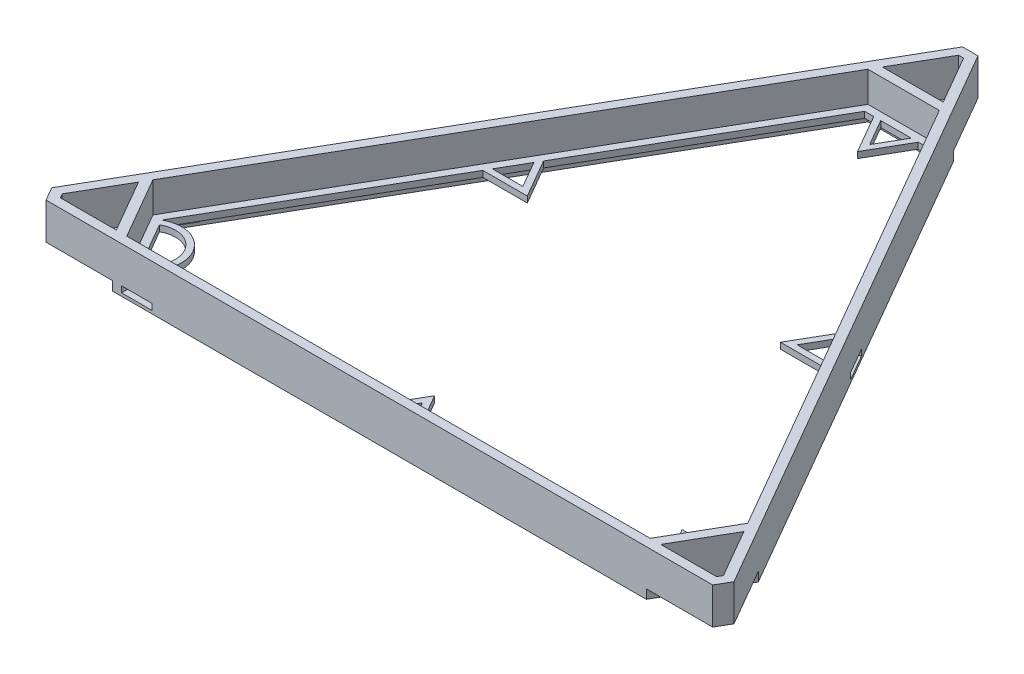
SolidWorks part; units mm, degrees
ref_plane "Front Plane" through (0, 0, 0) normal (0, 0, 1) x (1, 0, 0)
ref_plane "Top Plane" through (0, 0, 0) normal (0, 1, 0) x (1, 0, 0)
ref_plane "Right Plane" through (0, 0, 0) normal (1, 0, 0) x (0, 0, -1)
sketch "Sketch1" plane through (0, 0, 0) normal (0, 1, 0) x (1, 0, 0)
  line L17 (-4, 192.2576) -> (111, -6.9282) construction
  line L24 (4, 192.2576) -> (-111, -6.9282) construction
  line L25 (-115, 0) -> (115, 0) construction
  line L26 (0, -4.4282) -> (0, -1.4282) construction
  line L27 (-113, -3.4641) -> (-107, 0) construction
  line L28 (0, 192.2576) -> (0, 185.3294) construction
  line L29 (113, -3.4641) -> (107, 0) construction
  line L31 (-107.8246, -1.4282) -> (-108.6491, 0)
  line L39 (109.5566, -4.4282) -> (-109.5566, -4.4282)
  line L40 (-0.8246, 186.7576) -> (0.8246, 186.7576)
  line L41 (-109.5566, -4.4282) -> (-112.1132, 0)
  line L42 (-2.5566, 189.7576) -> (-112.1132, 0)
  line L43 (109.5566, -4.4282) -> (112.1132, 0)
  line L44 (-2.5566, 189.7576) -> (2.5566, 189.7576)
  line L45 (2.5566, 189.7576) -> (112.1132, 0)
  line L47 (108.6491, 0) -> (107.8246, -1.4282)
  line L50 (-99.4737, 15.8923) -> (-89.4737, -1.4282)
  line L51 (-107.8246, -1.4282) -> (-89.4737, -1.4282)
  line L52 (-99.4737, 15.8923) -> (-108.6491, 0)
  line L54 (89.4737, -1.4282) -> (107.8246, -1.4282)
  line L56 (89.4737, -1.4282) -> (99.4737, 15.8923)
  line L57 (99.4737, 15.8923) -> (108.6491, 0)
  line L58 (0, -1.4282) -> (0, 1.0718) construction
  line L59 (54.7369, 93.3788) -> (52.5718, 92.1288) construction
  line L62 (-10, 170.8653) -> (10, 170.8653)
  line L63 (-10, 170.8653) -> (-0.8246, 186.7576)
  line L64 (0.8246, 186.7576) -> (10, 170.8653)
  line L65 (94.4737, 7.2321) -> (91.8756, 8.7321) construction
  line L66 (-11.7321, 167.8653) -> (11.7321, 167.8653)
  line L67 (97.7417, 18.8923) -> (86.0096, -1.4282)
  line L68 (97.7417, 18.8923) -> (11.7321, 167.8653)
  line L69 (-54.7369, 93.3788) -> (-52.5718, 92.1288) construction
  line L71 (-94.4737, 7.2321) -> (-91.8756, 8.7321) construction
  line L72 (-97.7417, 18.8923) -> (-86.0096, -1.4282)
  line L73 (-86.0096, -1.4282) -> (86.0096, -1.4282)
  line L74 (-97.7417, 18.8923) -> (-11.7321, 167.8653)
  line L79 (91.8756, 8.7321) -> (89.7106, 9.9821) construction
  line L81 (0, 167.8653) -> (0, 165.3653) construction
  line L97 (-94.8549, 18.8923) -> (-84.5662, 1.0718) construction
  line L100 (-94.8549, 18.8923) -> (-93.8549, 17.1603) construction
  line L106 (-84.5662, 1.0718) -> (-85.5662, 2.8038) construction
  line L107 (-93.8549, 17.1603) -> (-85.5662, 2.8038)
  line L108 (50.0718, 96.4589) -> (55.0718, 87.7987)
  line L109 (41.6077, 85.7987) -> (56.2265, 85.7987)
  line L111 (50.0718, 96.4589) -> (45.0718, 87.7987)
  line L112 (45.0718, 87.7987) -> (55.0718, 87.7987)
  line L115 (56.2265, 85.7987) -> (94.8549, 18.8923)
  line L116 (48.9171, 98.4589) -> (10.2887, 165.3653)
  line L117 (41.6077, 85.7987) -> (48.9171, 98.4589)
  line L118 (-5, 165.3653) -> (5, 165.3653)
  line L121 (-55.0718, 87.7987) -> (-50.0718, 96.4589)
  line L122 (-5, 165.3653) -> (0, 156.7051)
  line L123 (5, 165.3653) -> (0, 156.7051)
  line L124 (-56.2265, 85.7987) -> (-94.8549, 18.8923)
  line L125 (0, 152.7051) -> (7.3094, 165.3653)
  line L126 (0, 152.7051) -> (-7.3094, 165.3653)
  line L127 (-10.2887, 165.3653) -> (-7.3094, 165.3653)
  line L128 (7.3094, 165.3653) -> (10.2887, 165.3653)
  line L129 (-50.0718, 96.4589) -> (-45.0718, 87.7987)
  line L130 (-55.0718, 87.7987) -> (-45.0718, 87.7987)
  line L131 (-48.9171, 98.4589) -> (-10.2887, 165.3653)
  line L132 (-41.6077, 85.7987) -> (-48.9171, 98.4589)
  line L133 (-41.6077, 85.7987) -> (-56.2265, 85.7987)
  line L134 (5, 1.0718) -> (-5, 1.0718)
  line L135 (-2.5, 5.4019) -> (-4.2321, 6.4019) construction
  line L136 (-5, 1.0718) -> (0, 9.7321)
  line L137 (0, 9.7321) -> (5, 1.0718)
  line L138 (2.5, 5.4019) -> (4.2321, 6.4019) construction
  line L139 (0, 13.7321) -> (-7.3094, 1.0718)
  line L141 (-7.3094, 1.0718) -> (-84.5662, 1.0718)
  line L143 (84.5662, 1.0718) -> (7.3094, 1.0718)
  line L144 (0, 13.7321) -> (7.3094, 1.0718)
  line L145 (92.2106, 14.3122) -> (87.2106, 5.6519)
  line L146 (84.7106, 9.9821) -> (82.9785, 8.9821) construction
  line L147 (87.2106, 5.6519) -> (82.2106, 14.3122)
  line L148 (82.2106, 14.3122) -> (92.2106, 14.3122)
  line L149 (87.2106, 14.3122) -> (87.2106, 16.3122) construction
  line L150 (94.8549, 18.8923) -> (93.3653, 16.3122)
  line L151 (78.7465, 16.3122) -> (86.0559, 3.6519)
  line L152 (78.7465, 16.3122) -> (93.3653, 16.3122)
  line L153 (86.0559, 3.6519) -> (84.5662, 1.0718)
  arc A0 (-94.8549, 18.8923) -> (-84.5662, 1.0718) centre (-89.7106, 9.9821) cw
  arc A1 (-93.8549, 17.1603) -> (-85.5662, 2.8038) centre (-89.7106, 9.9821) cw
  point P18 (0, -1.4282)
  point P41 (0, 167.8653)
  point P44 (91.8756, 8.7321)
  point P51 (-91.8756, 8.7321)
  point P55 (0, 1.0718)
  point P57 (-52.5718, 92.1288)
  point P61 (52.5718, 92.1288)
  point P65 (52.5718, 92.1288)
  point P69 (89.7106, 9.9821)
  point P74 (0, 165.3653)
  point P78 (-89.7106, 9.9821)
  point P79 (0, 165.3653)
  point P83 (-89.7106, 9.9821)
  point P89 (-52.5718, 92.1288)
  point P92 (0, 1.0718)
  point P97 (-45.8397, 93.1288)
  point P100 (-50.0718, 85.7987)
  point P106 (-4.2321, 6.4019)
  point P109 (4.2321, 6.4019)
  point P110 (89.7106, 9.9821)
  point P119 (82.9785, 8.9821)
  point P122 (87.2106, 16.3122)
  dimension "D1" = 8
  dimension "D2" = 8
  dimension "D3" = 8
  dimension "D4" = 230
  dimension "D5" = 230
  dimension "D6" = 230
  dimension "D7" = 3
  dimension "D8" = 3
  dimension "D9" = 3
  dimension "D10" = 2.5
  dimension "D11" = 2.5
  dimension "D12" = 2.5
  dimension "D13" = 2
  dimension "D14" = 2.5
  dimension "D15" = 2.5
  dimension "D16" = 2
  dimension "D17" = 10
  dimension "D18" = 10
  dimension "D19" = 10
  dimension "D20" = 10
  dimension "D21" = 2
  dimension "D22" = 2
  dimension "D23" = 10
  dimension "D24" = 2
  dimension "D25" = 2
extrude "Boss-Extrude1" add sketch "Sketch1" along normal blind 12 contours L45 L43 L39 L41 L42 L44 | L74 L66 L68 L67 L73 L72 | L52 L31 L51 L50 | L57 L47 L54 L56 | L64 L62 L63 L40
extrude "Boss-Extrude2" add sketch "Sketch1<4>" along normal blind 2 contours L74 L72 L73 L67 L68 L66 region at (0, 0, -167.6067)
sketch "Sketch1<4>" plane through (0, 0, 0) normal (0, 1, 0) x (1, 0, 0) same geometry as "Sketch1"
sketch "Sketch2" plane through (0, 0, 0) normal (0, -1, 0) x (1, 0, 0)
  line L24 (-2.5566, -189.7576) -> (-112.1132, 0) construction
  line L25 (109.5566, 4.4282) -> (-109.5566, 4.4282) construction
  line L27 (2.5566, -189.7576) -> (112.1132, 0) construction
  line L33 (-89.4737, 1.4282) -> (-101.2058, -18.8923) construction
  line L34 (-89.4737, 1.4282) -> (-87.7417, 4.4282) construction
  line L35 (-11.7321, -167.8653) -> (11.7321, -167.8653)
  line L36 (89.4737, 1.4282) -> (87.7417, 4.4282) construction
  line L37 (99.4737, -15.8923) -> (101.2058, -18.8923) construction
  line L38 (86.0096, 1.4282) -> (97.7417, -18.8923)
  line L40 (101.2058, -18.8923) -> (87.7417, 4.4282)
  line L42 (-10, -170.8653) -> (-13.4641, -170.8653) construction
  line L43 (10, -170.8653) -> (13.4641, -170.8653) construction
  line L44 (87.7417, 4.4282) -> (-87.7417, 4.4282)
  line L45 (-97.7417, -18.8923) -> (-86.0096, 1.4282)
  line L46 (57.3349, -94.8788) -> (54.7369, -93.3788) construction
  line L47 (0, 4.4282) -> (0, 1.4282) construction
  line L48 (-87.7417, 4.4282) -> (-101.2058, -18.8923)
  line L49 (11.7321, -167.8653) -> (97.7417, -18.8923)
  line L50 (-86.0096, 1.4282) -> (86.0096, 1.4282)
  line L51 (-57.3349, -94.8788) -> (-54.7369, -93.3788) construction
  line L52 (-11.7321, -167.8653) -> (-97.7417, -18.8923)
  line L53 (-101.2058, -18.8923) -> (-13.4641, -170.8653)
  line L54 (-13.4641, -170.8653) -> (13.4641, -170.8653)
  line L55 (13.4641, -170.8653) -> (101.2058, -18.8923)
  point P66 (0, -167.8653)
  point P68 (-91.8756, -8.7321)
  point P72 (54.7369, -93.3788)
  point P75 (0, 1.4282)
  point P80 (-54.7369, -93.3788)
  dimension "D4" = 3
  dimension "D5" = 3
  dimension "D6" = 3
extrude "Boss-Extrude3" add sketch "Sketch2" along normal blind 3
sketch "Sketch4" plane through (0, 0, 4.4282) normal (0, 0, 1) x (1, 0, 0)
  line L1 (-84.7417, 0) -> (-84.7417, -2)
  line L2 (-97.7417, 0) -> (-11.7321, 0) construction
  line L3 (-84.7417, -2) -> (-74.7417, -2)
  line L4 (-74.7417, -2) -> (-74.7417, 0)
  line L5 (-74.7417, 0) -> (-84.7417, 0)
  line L6 (-2.5566, 0) -> (-112.1132, 0) construction
  line L7 (-87.7417, 0) -> (-84.7417, 0) construction
  dimension "D1" = 3
  dimension "D2" = 2
  dimension "D3" = 10
extrude "Cut-Extrude1" cut sketch "Sketch4" against normal blind 6
sketch "Sketch5" plane through (-84.0849, 0, -48.5465) normal (-0.866, 0, -0.5) x (-0.5, 0, 0.866)
  line L0 (34.2417, 0) -> (31.2417, 0) construction
  line L1 (-50.9434, 0) -> (58.6132, 0) construction
  line L2 (31.2417, 0) -> (31.2417, -2)
  line L3 (31.2417, -2) -> (21.2417, -2)
  line L4 (21.2417, -2) -> (21.2417, 0)
  line L5 (21.2417, 0) -> (31.2417, 0)
  dimension "D1" = 3
  dimension "D2" = 2
  dimension "D3" = 10
extrude "Cut-Extrude2" cut sketch "Sketch5" against normal blind 6
sketch "Sketch6" plane through (84.0849, 0, -48.5465) normal (0.866, 0, -0.5) x (-0.5, 0, -0.866)
  line L0 (-34.2417, 0) -> (141.2417, 0) construction
  line L1 (58.5, 0) -> (48.5, 0)
  line L2 (48.5, 0) -> (48.5, -2)
  line L3 (48.5, -2) -> (58.5, -2)
  line L4 (58.5, -2) -> (58.5, 0)
  point P8 (53.5, 0)
  dimension "D1" = 10
  dimension "D2" = 2
extrude "Cut-Extrude3" cut sketch "Sketch6" against normal blind 6
